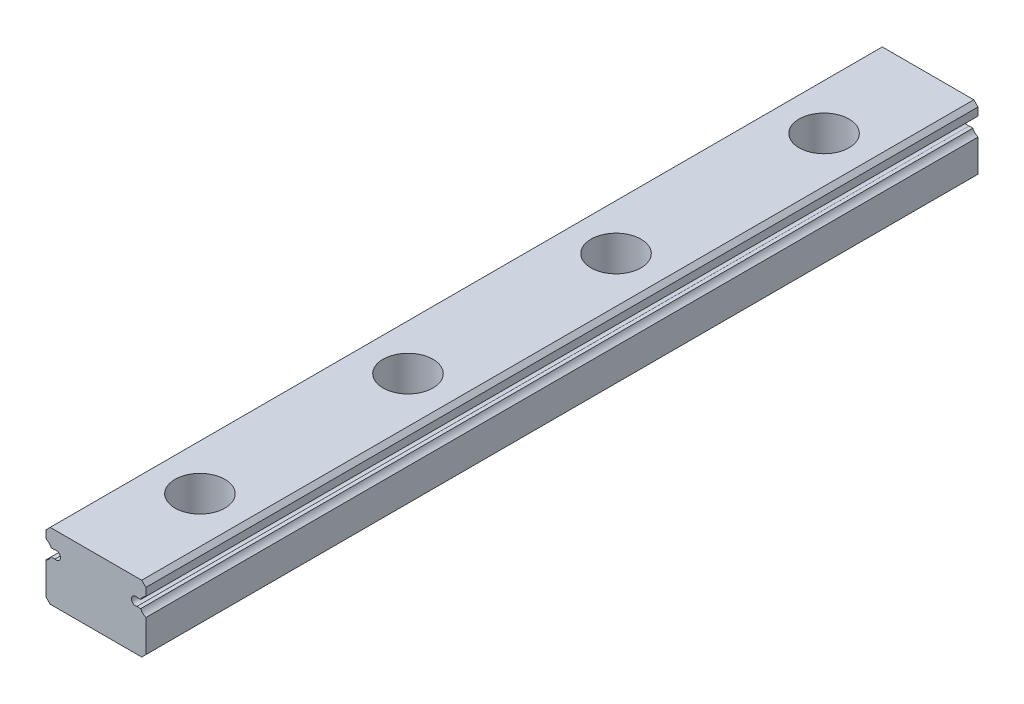
SolidWorks part; units mm, degrees
material "Chrome Stainless Steel"
ref_plane "Front Plane" through (0, 0, 0) normal (0, 0, 1) x (1, 0, 0)
ref_plane "Top Plane" through (0, 0, 0) normal (0, 1, 0) x (1, 0, 0)
ref_plane "Right Plane" through (0, 0, 0) normal (1, 0, 0) x (0, 0, -1)
sketch "Sketch1" plane through (0, 0, 0) normal (0, 0, 1) x (1, 0, 0)
  line L0 (0, 4) -> (0, -4) construction
  line L1 (5.5, -4) -> (-5.5, -4)
  line L2 (-5.5, -4) -> (-6, -3.5)
  line L3 (-6, -3.5) -> (-6, 0.3689)
  line L4 (5.5, 4) -> (-5.5, 4)
  line L5 (-5.5, 4) -> (-6, 3.5)
  line L6 (-6, 2.5511) -> (-6, 3.5)
  line L7 (-5.3839, 0.985) -> (-4.9211, 0.985)
  line L8 (-5.3839, 1.935) -> (-4.9211, 1.935)
  line L9 (5.3839, 0.985) -> (4.9211, 0.985)
  line L10 (5.5, 4) -> (6, 3.5)
  line L11 (6, 2.5511) -> (6, 3.5)
  line L12 (5.3839, 1.935) -> (4.9211, 1.935)
  line L13 (6, -3.5) -> (6, 0.3689)
  line L14 (5.5, -4) -> (6, -3.5)
  circle A0 centre (-6.475, 1.46) radius 1.19 construction
  circle A1 centre (-4.765, 1.46) radius 0.5 construction
  arc A2 (-6, 0.3689) -> (-5.3839, 0.985) centre (-6.475, 1.46) ccw
  arc A3 (-5.3839, 1.935) -> (-6, 2.5511) centre (-6.475, 1.46) ccw
  arc A4 (-4.9211, 0.985) -> (-4.9211, 1.935) centre (-4.765, 1.46) ccw
  arc A5 (5.3839, 1.935) -> (6, 2.5511) centre (6.475, 1.46) cw
  arc A6 (4.9211, 0.985) -> (4.9211, 1.935) centre (4.765, 1.46) cw
  arc A7 (6, 0.3689) -> (5.3839, 0.985) centre (6.475, 1.46) cw
  point P4 (0, 0)
  dimension "D5" = 5.46
  dimension "D6" = 6.475
  dimension "D7" = 2.38
  dimension "D11" = 1
  dimension "D12" = 5.46
  dimension "D13" = 4.765
  dimension "D1" = 8
  dimension "D2" = 0.5
  dimension "D3" = 0.5
  dimension "D4" = 6
  dimension "D8" = 0.5
  dimension "D9" = 0.5
  dimension "D10" = 6
  dimension "D14" = 0.475
  dimension "D15" = 0.475
extrude "Boss-Extrude1" add sketch "Sketch1" along normal blind 100 contours L13 A7 L9 A6 L12 A5 L11 L10 L4 L5 L6 A3 L8 A4 L7 A2 L3 L2 L1 L14 region at (0, -0.0654, 0)
sketch "Sketch2" plane through (0, 4, 0) normal (0, 1, 0) x (1, 0, 0)
  line L0 (5.5, 0) -> (-5.5, 0) construction
  circle A0 centre (0, -12.5) radius 3
  dimension "D1" = 12.5
extrude "Cut-Extrude1" cut sketch "Sketch2" against normal blind 4.5
sketch "Sketch3" plane through (0, -0.5, 0) normal (0, 1, 0) x (1, 0, 0)
  circle A0 centre (0, -12.5) radius 1.75
extrude "Cut-Extrude2" cut sketch "Sketch3" against normal through all
pattern_linear "LPattern1" count 4 spacing 25 along (0, 0, 1) of "Cut-Extrude1", "Cut-Extrude2"
